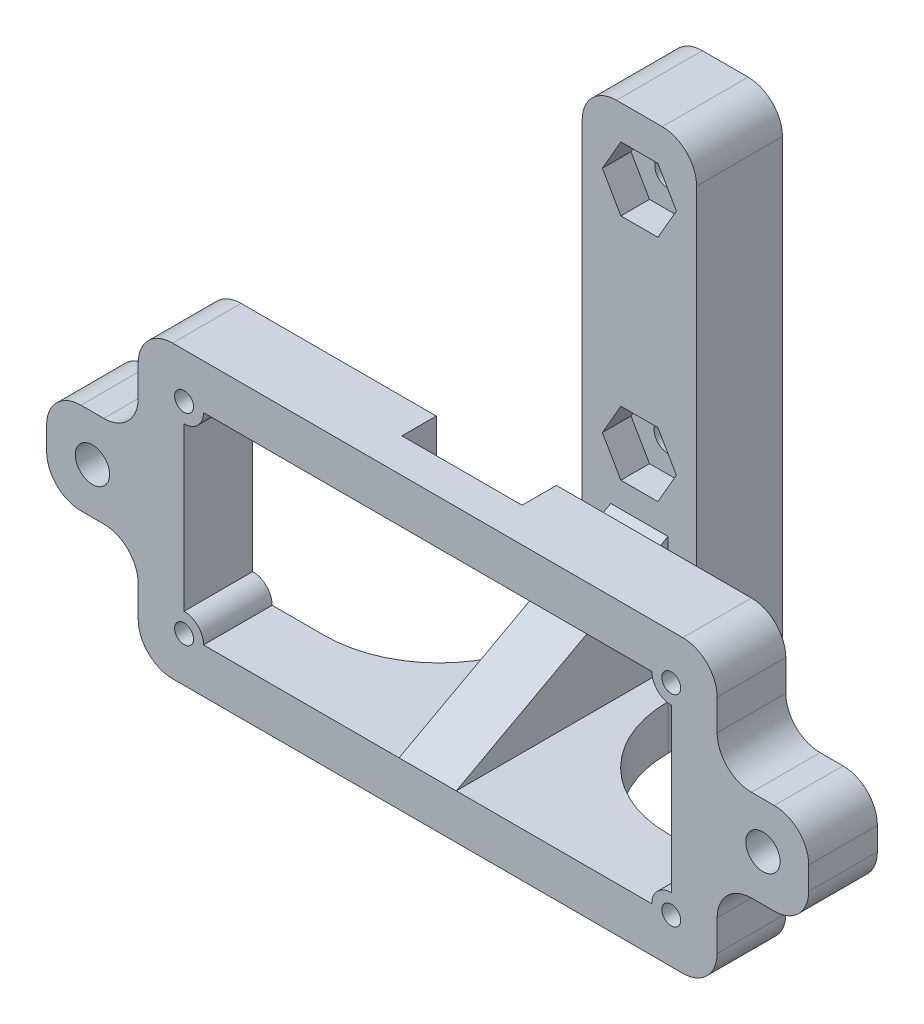
SolidWorks part; units mm, degrees
ref_plane "Plan de face" through (0, 0, 0) normal (0, 0, 1) x (1, 0, 0)
ref_plane "Plan de dessus" through (0, 0, 0) normal (0, 1, 0) x (1, 0, 0)
ref_plane "Plan de droite" through (0, 0, 0) normal (1, 0, 0) x (0, 0, -1)
sketch "Esquisse1" plane through (0, 0, 0) normal (0, 0, 1) x (1, 0, 0)
  line L0 (-21.285, -8.79) -> (21.285, -8.79) construction
  line L1 (-21.285, -8.79) -> (-21.285, 8.79) construction
  line L2 (-21.285, 8.79) -> (21.285, 8.79) construction
  line L3 (21.285, -8.79) -> (21.285, 8.79) construction
  line L4 (-21.285, -8.79) -> (21.285, 8.79) construction
  line L5 (-21.285, 8.79) -> (21.285, -8.79) construction
  line L6 (-22.795, -10.2) -> (22.795, -10.2)
  line L7 (-22.795, -10.2) -> (-22.795, 10.2)
  line L8 (-22.795, 10.2) -> (22.795, 10.2)
  line L9 (22.795, -10.2) -> (22.795, 10.2)
  line L10 (-22.795, -10.2) -> (22.795, 10.2) construction
  line L11 (-22.795, 10.2) -> (22.795, -10.2) construction
  circle A0 centre (-21.285, 8.79) radius 0.825
  circle A1 centre (21.285, 8.79) radius 0.825
  circle A2 centre (21.285, -8.79) radius 0.825
  circle A3 centre (-21.285, -8.79) radius 0.825
  point P0 (0, 0)
  point P5 (0, 0)
  dimension "D5" = 1.65
  dimension "D1" = 42.57
  dimension "D2" = 17.58
  dimension "D3" = 20.4
  dimension "D4" = 45.59
extrude "Boss.-Extru.1" add sketch "Esquisse1" along normal blind 6
sketch "Esquisse3" plane through (0, 0, 6) normal (0, 0, 1) x (1, 0, 0)
  line L0 (22.795, 10.2) -> (-22.795, 10.2) construction
  line L1 (-25.295, 12.7) -> (25.295, 12.7)
  line L2 (-25.295, 12.7) -> (-25.295, -12.7)
  line L3 (-25.295, -12.7) -> (25.295, -12.7)
  line L4 (25.295, 12.7) -> (25.295, -12.7)
  line L5 (-25.295, 12.7) -> (25.295, -12.7) construction
  line L6 (-25.295, -12.7) -> (25.295, 12.7) construction
  line L7 (-22.795, 10.2) -> (-22.795, -10.2) construction
  line L9 (22.795, -10.2) -> (-22.795, -10.2)
  line L10 (22.795, -10.2) -> (22.795, 10.2)
  line L11 (22.795, 10.2) -> (-22.795, 10.2)
  line L12 (-22.795, -10.2) -> (-22.795, 10.2)
  line L13 (22.795, -10.2) -> (-22.795, 10.2) construction
  line L14 (22.795, 10.2) -> (-22.795, -10.2) construction
  point P0 (0, 0)
  point P10 (0, 0)
  dimension "D1" = 2.5
  dimension "D2" = 2.5
extrude "Boss.-Extru.2" add sketch "Esquisse3" against normal blind 6
sketch "Esquisse4" plane through (0, 0, 6) normal (0, 0, 1) x (1, 0, 0)
  line L1 (19.585, -8.79) -> (-19.585, -8.79)
  line L2 (21.285, -7.09) -> (21.285, 7.09)
  line L3 (19.585, 8.79) -> (-19.585, 8.79)
  line L4 (-21.285, -7.09) -> (-21.285, 7.09)
  line L5 (21.285, -8.79) -> (-21.285, 8.79) construction
  line L6 (21.285, 8.79) -> (-21.285, -8.79) construction
  arc A0 (-19.585, 8.79) -> (-21.285, 7.09) centre (-21.285, 8.79) cw
  arc A1 (21.285, 7.09) -> (19.585, 8.79) centre (21.285, 8.79) cw
  arc A2 (19.585, -8.79) -> (21.285, -7.09) centre (21.285, -8.79) cw
  arc A3 (-19.585, -8.79) -> (-21.285, -7.09) centre (-21.285, -8.79) ccw
  point P0 (0, 0)
  dimension "D1" = 1.7
extrude "Enlèv. mat.-Extru.1" cut sketch "Esquisse4" against normal blind 6
sketch "Esquisse5" plane through (0, 0, 0) normal (0, 0, -1) x (-1, 0, 0)
  line L0 (19.585, -8.79) -> (-19.585, -8.79) construction
  line L1 (-5, -12.7) -> (5, -12.7)
  line L2 (-5, -12.7) -> (-5, -8.79)
  line L3 (-5, -8.79) -> (5, -8.79)
  line L4 (5, -12.7) -> (5, -8.79)
  line L5 (-5, -12.7) -> (5, -8.79) construction
  line L6 (-5, -8.79) -> (5, -12.7) construction
  line L7 (25.295, -12.7) -> (-25.295, -12.7) construction
  point P0 (0, -10.745)
  dimension "D1" = 10
extrude "Boss.-Extru.5" add sketch "Esquisse5" along normal blind 20
sketch "Esquisse7" plane through (0, 12.7, 0) normal (0, 1, 0) x (1, 0, 0)
  line L0 (25.295, 0) -> (-25.295, 0) construction
  line L1 (-5.25, -3) -> (5.25, -3)
  line L2 (-5.25, -3) -> (-5.25, 0)
  line L3 (-5.25, 0) -> (5.25, 0)
  line L4 (5.25, -3) -> (5.25, 0)
  line L5 (-5.25, -3) -> (5.25, 0) construction
  line L6 (-5.25, 0) -> (5.25, -3) construction
  point P0 (0, -1.5)
  dimension "D1" = 10.5
  dimension "D2" = 3
extrude "Enlèv. mat.-Extru.2" cut sketch "Esquisse7" against normal blind 5
sketch "Esquisse8" plane through (0, -12.7, 0) normal (0, -1, 0) x (1, 0, 0)
  line L0 (-25.295, 6) -> (25.295, 6) construction
  line L1 (-6.1299, 0) -> (6.1299, 0)
  line L2 (-6.1299, 0) -> (-6.1299, 6)
  line L3 (-6.1299, 6) -> (6.1299, 6)
  line L4 (6.1299, 0) -> (6.1299, 6)
  line L5 (-6.1299, 0) -> (6.1299, 6) construction
  line L6 (-6.1299, 6) -> (6.1299, 0) construction
  point P0 (0, 3)
  dimension "D1" = 6
extrude "Boss.-Extru.6" [suppressed] add sketch "Esquisse8" along normal blind 7
sketch "Esquisse9" [suppressed] plane through (0, 0, 0) normal (0, 0, -1) x (-1, 0, 0)
  line L0 (-6.1299, -19.7) -> (-6.1299, -12.7) construction
  circle A0 centre (0, -16.2) radius 1.6
  point P5 (-6.1299, -16.2)
  dimension "D1" = 3.2
extrude "Enlèv. mat.-Extru.3" [suppressed] cut sketch "Esquisse9" against normal blind 6
sketch "Esquisse10" [suppressed] plane through (0, 0, 0) normal (0, 0, -1) x (-1, 0, 0)
  line L0 (6.1299, -19.7) -> (-6.1299, -19.7) construction
  line L1 (3.2332, -16.2) -> (1.6166, -13.4)
  line L2 (1.6166, -13.4) -> (-1.6166, -13.4)
  line L3 (-1.6166, -13.4) -> (-3.2332, -16.2)
  line L4 (-3.2332, -16.2) -> (-1.6166, -19)
  line L5 (-1.6166, -19) -> (1.6166, -19)
  line L6 (1.6166, -19) -> (3.2332, -16.2)
  circle A0 centre (0, -16.2) radius 2.8 construction
  dimension "D1" = 5.6
extrude "Enlèv. mat.-Extru.4" [suppressed] cut sketch "Esquisse10" against normal blind 2.5
fillet "Congé1" [suppressed] radius 3
fillet "Congé2" radius 3 4 edges at (25.295, -12.7, 3) (25.295, 12.7, 3) (-25.295, 12.7, 3) (-25.295, -12.7, 3)
sketch "Esquisse11" plane through (0, 0, -20) normal (0, 0, -1) x (-1, 0, 0)
  line L0 (-5, -12.7) -> (-22.295, -12.7) construction
  line L1 (-5, -12.7) -> (5, -12.7)
  line L2 (-5, -12.7) -> (-5, 31.9727)
  line L3 (-5, 31.9727) -> (5, 31.9727)
  line L4 (5, -12.7) -> (5, 31.9727)
  line L7 (0, 26.21) -> (0, 6.21) construction
  line L10 (5, -8.79) -> (-5, -8.79) construction
  circle A0 centre (0, 26.21) radius 1.1581
  circle A3 centre (0, 6.21) radius 1.2189
  point P6 (0, 31.9727)
  dimension "D1" = 20
  dimension "D2" = 15
  dimension "D4" = 5
extrude "Boss.-Extru.7" add sketch "Esquisse11" against normal blind 7.5
fillet "Congé3" radius 3 2 edges at (5, 31.9727, -16.25) (-5, 31.9727, -16.25)
sketch "Esquisse12" plane through (0, 0, -12.5) normal (0, 0, 1) x (1, 0, 0)
  line L0 (-2, 31.9727) -> (2, 31.9727) construction
  line L7 (1.6166, 29.01) -> (-1.6166, 29.01)
  line L8 (-1.6166, 29.01) -> (-3.2332, 26.21)
  line L9 (-3.2332, 26.21) -> (-1.6166, 23.41)
  line L10 (-1.6166, 23.41) -> (1.6166, 23.41)
  line L11 (1.6166, 23.41) -> (3.2332, 26.21)
  line L12 (3.2332, 26.21) -> (1.6166, 29.01)
  line L13 (-1.6166, 9.01) -> (-3.2332, 6.21)
  line L14 (-3.2332, 6.21) -> (-1.6166, 3.41)
  line L15 (-1.6166, 3.41) -> (1.6166, 3.41)
  line L16 (1.6166, 3.41) -> (3.2332, 6.21)
  line L17 (3.2332, 6.21) -> (1.6166, 9.01)
  line L18 (1.6166, 9.01) -> (-1.6166, 9.01)
  circle A1 centre (0, 26.21) radius 2.8 construction
  circle A2 centre (0, 6.21) radius 2.8 construction
  point P2 (0, 0)
  dimension "D1" = 5.6
extrude "Enlèv. mat.-Extru.5" cut sketch "Esquisse12" against normal blind 2.5
sketch "Esquisse13" plane through (5, 0, 0) normal (1, 0, 0) x (0, 0, -1)
  line L0 (-6, -8.79) -> (12.5, 11.21)
  line L1 (12.5, 11.21) -> (12.5, -8.79)
  line L2 (12.5, -8.79) -> (0, -8.79) construction
  line L3 (12.5, -8.79) -> (-6, -8.79)
  line L4 (12.5, 28.9727) -> (12.5, -8.79) construction
  dimension "D1" = 20
extrude "Boss.-Extru.8" [suppressed] add sketch "Esquisse13" against normal blind 5 from offset 5 offset against normal yes
fillet "Congé4" [suppressed] radius 3
fillet "Congé5" [suppressed] radius 3
sketch "Esquisse14" plane through (-25.295, 0, 0) normal (-1, 0, 0) x (0, 0, 1)
  line L0 (0, 9.7) -> (0, -9.7) construction
  line L1 (0, 4) -> (6, 4)
  line L2 (0, 4) -> (0, -4)
  line L3 (0, -4) -> (6, -4)
  line L4 (6, 4) -> (6, -4)
  line L5 (6, 9.7) -> (6, -9.7) construction
  dimension "D1" = 8
extrude "Boss.-Extru.9" add sketch "Esquisse14" along normal blind 8
sketch "Esquisse15" plane through (25.295, 0, 0) normal (1, 0, 0) x (0, 0, -1)
  line L5 (0, -9.7) -> (0, 9.7) construction
  line L6 (0, 4) -> (-6, 4)
  line L7 (0, 4) -> (0, -4)
  line L8 (0, -4) -> (-6, -4)
  line L9 (-6, 4) -> (-6, -4)
  line L10 (-6, -9.7) -> (-6, 9.7) construction
  line L11 (-6, 9.7) -> (-6, -9.7) construction
  point P4 (-6, 0)
  dimension "D1" = 8
extrude "Boss.-Extru.10" add sketch "Esquisse15" along normal blind 8
sketch "Esquisse16" plane through (0, 0, 6) normal (0, 0, 1) x (1, 0, 0)
  line L0 (-33.295, 4) -> (-25.295, 4) construction
  line L1 (-33.295, -4) -> (-33.295, 4) construction
  line L2 (33.295, 4) -> (25.295, 4) construction
  circle A0 centre (-29.295, 0) radius 1.5
  circle A1 centre (29.295, 0) radius 1.5
  point P7 (-29.295, 4)
  point P10 (-33.295, 0)
  point P13 (29.295, 4)
  dimension "D1" = 3
  dimension "D2" = 3
extrude "Enlèv. mat.-Extru.6" cut sketch "Esquisse16" against normal blind 6
sketch "Esquisse17" plane through (0, 0, 6) normal (0, 0, 1) x (1, 0, 0)
  line L1 (-26.0618, 0) -> (-27.6784, 2.8)
  line L2 (-27.6784, 2.8) -> (-30.9116, 2.8)
  line L3 (-30.9116, 2.8) -> (-32.5282, 0)
  line L4 (-32.5282, 0) -> (-30.9116, -2.8)
  line L5 (-30.9116, -2.8) -> (-27.6784, -2.8)
  line L6 (-27.6784, -2.8) -> (-26.0618, 0)
  line L7 (32.5282, 0) -> (30.9116, 2.8)
  line L8 (30.9116, 2.8) -> (27.6784, 2.8)
  line L9 (27.6784, 2.8) -> (26.0618, 0)
  line L10 (26.0618, 0) -> (27.6784, -2.8)
  line L11 (27.6784, -2.8) -> (30.9116, -2.8)
  line L12 (30.9116, -2.8) -> (32.5282, 0)
  circle A0 centre (-29.295, 0) radius 2.8 construction
  circle A1 centre (29.295, 0) radius 2.8 construction
  dimension "D1" = 5.6
  dimension "D2" = 5.6
extrude "Enlèv. mat.-Extru.7" cut sketch "Esquisse17" against normal blind 2.5 from offset 3.5 offset against normal yes
fillet "Congé6" radius 3 8 edges at (-25.295, -4, 3) (-33.295, -4, 3) (-33.295, 4, 3) (-25.295, 4, 3) (25.295, 4, 3) (33.295, 4, 3) (33.295, -4, 3) (25.295, -4, 3)
fillet "Congé7" radius 10 2 edges at (-5, -10.745, 0) (5, -10.745, 0)
sketch "Esquisse18" plane through (5, 0, 0) normal (1, 0, 0) x (0, 0, -1)
  line L0 (-6, -8.79) -> (12.5, 1.21)
  line L1 (12.5, 28.9727) -> (12.5, -8.79) construction
  line L3 (12.5, -8.79) -> (-6, -8.79)
  line L4 (12.5, -8.79) -> (12.5, 1.21)
  dimension "D1" = 10
extrude "Boss.-Extru.11" add sketch "Esquisse18" against normal blind 5 from offset 2.5 offset against normal yes
